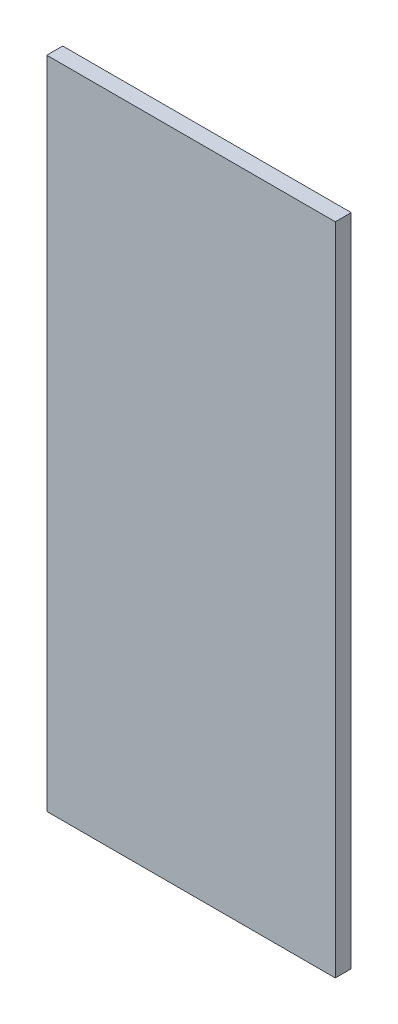
SolidWorks part; units mm, degrees
material "Perspex (TM) GS Acrylic Cast Sheet"
ref_plane "Front Plane" through (0, 0, 0) normal (0, 0, 1) x (1, 0, 0)
ref_plane "Top Plane" through (0, 0, 0) normal (0, 1, 0) x (1, 0, 0)
ref_plane "Right Plane" through (0, 0, 0) normal (1, 0, 0) x (0, 0, -1)
sketch "Sketch1" plane through (0, 0, 0) normal (0, 0, 1) x (1, 0, 0)
  line L1 (-81.5, -185) -> (81.5, -185)
  line L2 (-81.5, -185) -> (-81.5, 185)
  line L3 (-81.5, 185) -> (81.5, 185)
  line L4 (81.5, -185) -> (81.5, 185)
  line L5 (-81.5, -185) -> (81.5, 185) construction
  line L6 (-81.5, 185) -> (81.5, -185) construction
  point P0 (0, 0)
  dimension "D1" = 163
  dimension "D2" = 370
extrude "Boss-Extrude1" add sketch "Sketch1" along normal blind 9
equation "\"PCLength\"= 145mm'Length across I/O from PS to GPU"
equation "\"PCWidth\"= 340mm'Distance of longest part parallel to GPU(ussually GPU)"
equation "\"PCHeight\"= 180mm'Tallest point with mobo laying flat"
equation "\"WallThickness\"= 9mm'Thickness of each outer tank wall"
equation "\"ThermoBarrierThickness\"= 6mm'Thickness of barrier between hot side and cold side"
equation "\"HotSideGap\"= 36mm'Space in the hot side for a pump"
equation "\"PCClearance\"= 30mm'Clearance from top of tank to top of PC"
equation "\"RadiatorHeight\"= 275mm'Final Height from ground of radiators"
equation "\"D1@Sketch1\"=\"PCLength\" + (2 * \"WallThickness\")"
equation "\"D2@Sketch1\"=\"PCWidth\" + \"PCClearance\""
equation "\"D1@Boss-Extrude1\"=\"WallThickness\""
